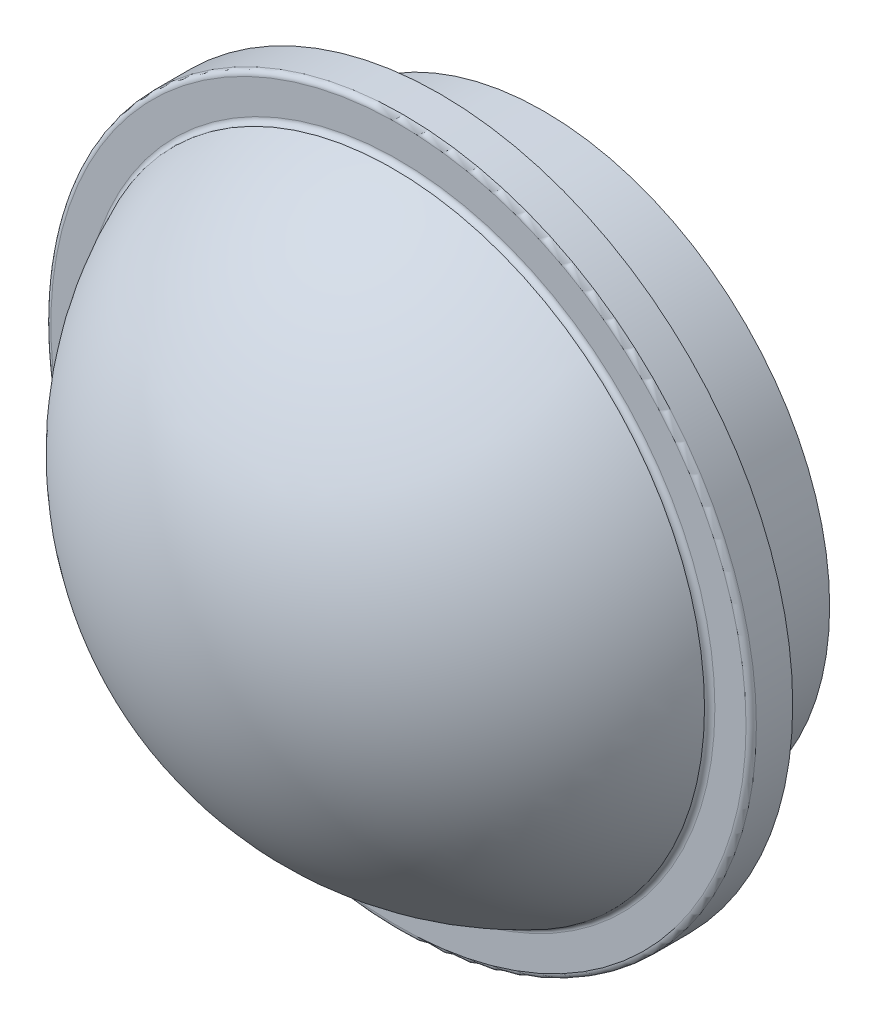
SolidWorks part; units mm, degrees
material "Verre"
ref_plane "Plan de face" through (0, 0, 0) normal (0, 0, 1) x (1, 0, 0)
ref_plane "Plan de dessus" through (0, 0, 0) normal (0, 1, 0) x (1, 0, 0)
ref_plane "Plan de droite" through (0, 0, 0) normal (1, 0, 0) x (0, 0, -1)
sketch "Esquisse1" plane through (0, 0, 0) normal (0, 0, 1) x (1, 0, 0)
  circle A0 centre (0, 0) radius 17
extrude "Boss.-Extru.1" add sketch "Esquisse1" along normal blind 2
sketch "Esquisse2" plane through (0, 0, 0) normal (0, 0, -1) x (-1, 0, 0)
  circle A0 centre (0, 0) radius 13.78
  circle A1 centre (0, 0) radius 11
extrude "Boss.-Extru.2" add sketch "Esquisse2" along normal blind 5
sketch "Esquisse3" plane through (0, 0, 2) normal (0, 0, 1) x (1, 0, 0)
  circle A0 centre (0, 0) radius 15
extrude "Boss.-Extru.3" add sketch "Esquisse3" along normal blind 0.25
dome "Dôme1" faces to dome 1 distance 10 reverse direction no elliptical dome no face at (15, 0, 2.25) parameters "D1"=10
dome "Dôme2" faces to dome 1 distance 11 reverse direction yes elliptical dome no face at (-11, 0, 0) parameters "D1"=11
fillet "Congé1" radius 0.25 2 edges at (15, 0, 2) (17, 0, 2)
